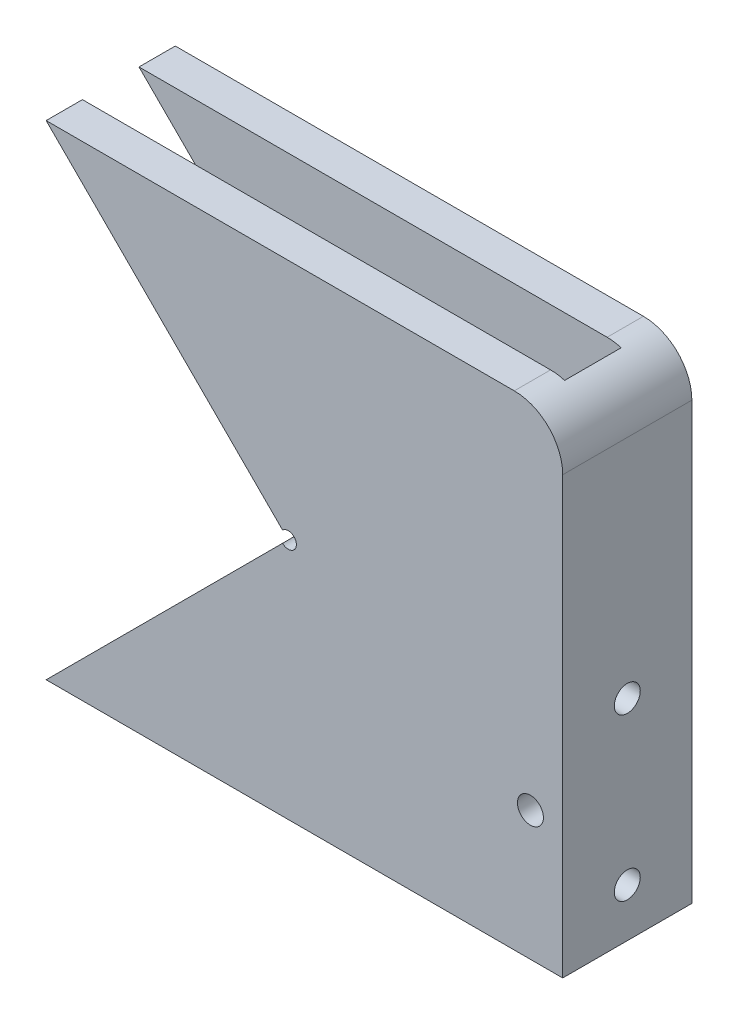
SolidWorks part; units mm, degrees
material "AISI Type A2 Tool Steel"
ref_plane "Front" through (0, 0, 0) normal (0, 0, 1) x (1, 0, 0)
ref_plane "Top" through (0, 0, 0) normal (0, 1, 0) x (1, 0, 0)
ref_plane "Right" through (0, 0, 0) normal (1, 0, 0) x (0, 0, -1)
sketch "Sketch1" plane through (0, 0, 0) normal (0, 0, 1) x (1, 0, 0)
  line L0 (-23.8125, -23.8125) -> (77.7875, -23.8125)
  line L1 (77.7875, -23.8125) -> (77.7875, 23.8125)
  line L2 (77.7875, 23.8125) -> (23.8125, 23.8125)
  line L3 (23.8125, 23.8125) -> (-23.8125, -23.8125)
  dimension "D1" = 45
  dimension "D2" = 101.6
  dimension "D3" = 47.625
extrude "Boss-Extrude1" add sketch "Sketch1" along normal mid plane 25.4 contours L3 L0 L1 L2
sketch "Sketch2" plane through (0, 0, 0) normal (-0.7071, 0.7071, 0) x (0, 0, 1)
  line L1 (-5.5626, -33.676) -> (5.5626, -33.676)
  line L2 (-5.5626, -33.676) -> (-5.5626, 33.676)
  line L3 (-5.5626, 33.676) -> (5.5626, 33.676)
  line L4 (5.5626, -33.676) -> (5.5626, 33.676)
  line L5 (-5.5626, -33.676) -> (5.5626, 33.676) construction
  line L6 (-5.5626, 33.676) -> (5.5626, -33.676) construction
  line L7 (12.7, 33.676) -> (-12.7, 33.676) construction
  line L8 (12.7, -33.676) -> (-12.7, -33.676) construction
  point P0 (0, 0)
  dimension "D1" = 11.1252
extrude "Cut-Extrude1" cut sketch "Sketch2" against normal through all
mirror "Mirror1" about plane through (77.7875, 23.8125, 12.7) normal (0, -1, 0) of "Boss-Extrude1", "Cut-Extrude1"
fillet "Fillet1" radius 9.525 1 edges at (77.7875, 71.4375, 0)
sketch "Sketch3" plane through (0, 0, 12.7) normal (0, 0, 1) x (1, 0, 0)
  circle A0 centre (23.8125, 23.8125) radius 1.5875
  dimension "D1" = 3.175
extrude "Cut-Extrude2" cut sketch "Sketch3" against normal through all
hole_wizard "1/4-20 Tapped Hole1" positions "Sketch4" profile "Sketch5" tap size "1/4-20" standard "ANSI Inch" end condition through all
sketch "Sketch4" plane through (0, 0, 12.7) normal (0, 0, 1) x (1, 0, 0)
  line L0 (77.7875, -23.8125) -> (77.7875, 61.9125) construction
  line L1 (-23.8125, -23.8125) -> (77.7875, -23.8125) construction
  point P0 (71.4375, 1.5875)
  dimension "D1" = 6.35
  dimension "D2" = 25.4
sketch "Sketch5" plane through (71.4375, 1.5875, 12.7) normal (1, 0, 0) x (0, -1, 0)
  line L0 (0, 0) -> (0, 25.4)
  line L1 (0, 25.4) -> (2.5527, 25.4)
  line L2 (2.5527, 25.4) -> (2.5527, 0)
  line L5 (2.5527, 0) -> (0, 0)
  line L11 (0, -6.35) -> (0, 107.95) construction
  dimension "Thru Tap Drill Dia." = 5.1054
  dimension "Thru Tap Drill Depth" = 25.4
cosmetic thread "Hole Thread1" parameters "D2"=6.35
hole_wizard "1/4-20 Tapped Hole2" positions "Sketch6" profile "Sketch7" tap size "1/4-20" standard "ANSI Inch"
sketch "Sketch6" plane through (77.7875, 0, 0) normal (1, 0, 0) x (0, 0, -1)
  line L0 (12.7, -23.8125) -> (12.7, 61.9125) construction
  line L1 (-12.7, -23.8125) -> (12.7, -23.8125) construction
  point P0 (0, 17.4625)
  point P7 (0, -23.8125)
  dimension "D1" = 12.7
  dimension "D2" = 41.275
sketch "Sketch7" plane through (77.7875, 17.4625, 0) normal (0, 1, 0) x (0, 0, -1)
  line L0 (0, 0) -> (0, 17.4088)
  line L1 (0, 17.4088) -> (2.5527, 15.875)
  line L2 (2.5527, 15.875) -> (2.5527, 0)
  line L5 (2.5527, 0) -> (0, 0)
  line L10 (0, 17.4088) -> (-2.5527, 15.875) construction
  line L11 (0, -6.35) -> (0, 107.95) construction
  dimension "Tap Drill Dia." = 5.1054
  dimension "Tap Drill Depth" = 15.875
  dimension "Drill Angle" = 118
cosmetic thread "Hole Thread2" parameters "D1"=15.875, "D2"=6.35
hole_wizard "1/4-20 Tapped Hole3" positions "Sketch8" profile "Sketch9" tap size "1/4-20" standard "ANSI Inch" end condition through all
sketch "Sketch8" plane through (77.7875, 0, 0) normal (1, 0, 0) x (0, 0, -1)
  line L0 (-12.7, -23.8125) -> (12.7, -23.8125) construction
  line L1 (12.7, -23.8125) -> (12.7, 61.9125) construction
  point P0 (0, -14.2875)
  dimension "D1" = 9.525
  dimension "D2" = 12.7
sketch "Sketch9" plane through (77.7875, -14.2875, 0) normal (0, 1, 0) x (0, 0, -1)
  line L0 (0, 0) -> (0, 101.6)
  line L1 (0, 101.6) -> (2.5527, 101.6)
  line L2 (2.5527, 101.6) -> (2.5527, 0)
  line L5 (2.5527, 0) -> (0, 0)
  line L11 (0, -6.35) -> (0, 107.95) construction
  dimension "Thru Tap Drill Dia." = 5.1054
  dimension "Thru Tap Drill Depth" = 101.6
cosmetic thread "Hole Thread3" parameters "D2"=6.35
